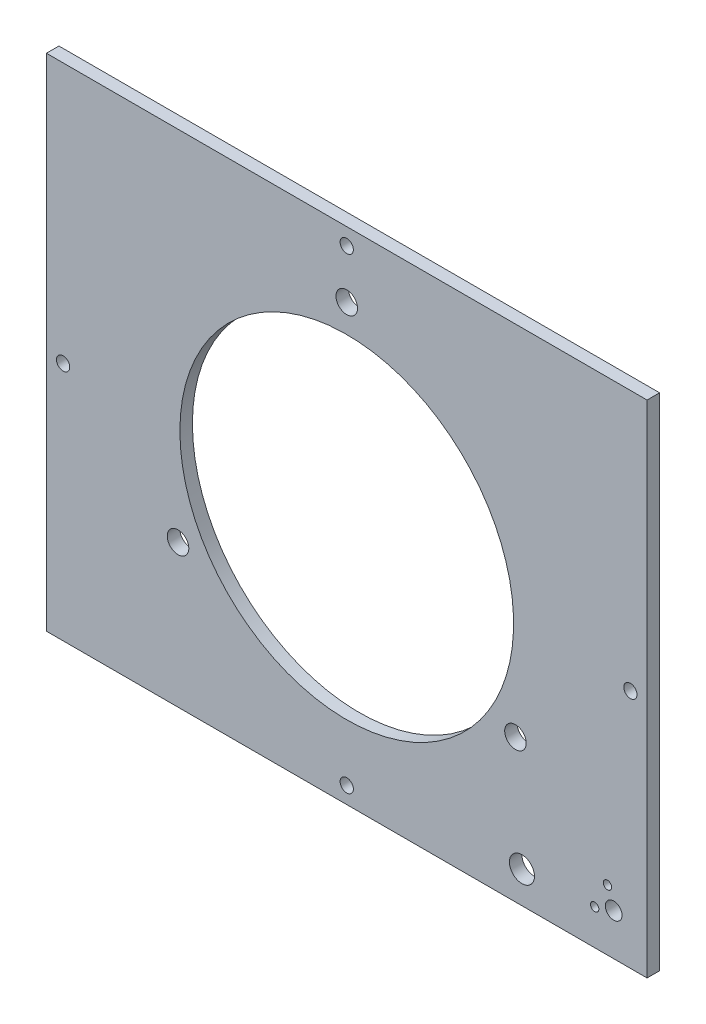
SolidWorks part; units mm, degrees
ref_plane "Front Plane" through (0, 0, 0) normal (0, 0, 1) x (1, 0, 0)
ref_plane "Top Plane" through (0, 0, 0) normal (0, 1, 0) x (1, 0, 0)
ref_plane "Right Plane" through (0, 0, 0) normal (1, 0, 0) x (0, 0, -1)
sketch "Sketch1" plane through (0, 0, 0) normal (0, 0, 1) x (1, 0, 0)
  line L0 (-228.6, -30.48) -> (-228.6, -182.88)
  line L1 (-228.6, -182.88) -> (228.6, -182.88)
  line L2 (-228.6, -182.88) -> (-228.6, 198.12) construction
  line L3 (-228.6, 198.12) -> (228.6, 198.12) construction
  line L4 (228.6, -182.88) -> (228.6, 198.12) construction
  line L5 (228.6, -30.48) -> (228.6, -182.88)
  line L6 (203.2, -151.13) -> (188.7233, -155.8925) construction
  line L7 (203.2, -151.13) -> (198.4375, -136.6533) construction
  line L10 (-228.6, -30.48) -> (-228.6, 198.12)
  line L11 (-228.6, 198.12) -> (228.6, 198.12)
  line L12 (228.6, -30.48) -> (228.6, 198.12)
  circle A0 centre (0, 0) radius 127
  circle A1 centre (0, 148.2852) radius 8.1988
  circle A3 centre (128.4188, -74.1426) radius 8.1988
  circle A4 centre (-128.4188, -74.1426) radius 8.1988
  circle A5 centre (203.2, -151.13) radius 6.35
  circle A6 centre (188.7233, -155.8925) radius 3.175
  circle A7 centre (198.4375, -136.6533) radius 3.175
  circle A8 centre (133.35, -158.75) radius 9.525
  point P19 (0, 0)
  dimension "D1" = 254
  dimension "D4" = 182.88
  dimension "D5" = 228.6
  dimension "D6" = 148.2852
  dimension "D8" = 12.7
  dimension "D9" = 31.75
  dimension "D10" = 25.4
  dimension "D11" = 15.24
  dimension "D12" = 6.35
  dimension "D13" = 26.9875
  dimension "D16" = 19.05
  dimension "D17" = 24.13
  dimension "D18" = 95.25
  dimension "D2" = 457.2
  dimension "D3" = 381
  dimension "D15" = 90
  dimension "D7" = 3
  dimension "D14" = 2
extrude "Boss-Extrude1" add sketch "Sketch1" along normal blind 9.525
sketch "Sketch2" plane through (0, 0, 9.525) normal (0, 0, 1) x (1, 0, 0)
  line L0 (-228.6, -182.88) -> (228.6, -182.88) construction
  line L1 (-228.6, 198.12) -> (-228.6, -182.88) construction
  line L2 (228.6, 198.12) -> (-228.6, 198.12) construction
  line L3 (228.6, -182.88) -> (228.6, 198.12) construction
  point P0 (0, 185.42)
  point P1 (-215.9, 0)
  point P2 (0, -170.18)
  point P3 (215.9, 0)
  point P4 (0, -182.88)
  dimension "D1" = 12.7
  dimension "D2" = 12.7
  dimension "D3" = 12.7
  dimension "D4" = 12.7
hole_wizard "3/8 Clearance Hole1" positions "Sketch4" profile "Sketch3" hole size "3/8" standard "ANSI Inch"
sketch "Sketch4" plane through (0, 0, 9.525) normal (0, 0, 1) x (1, 0, 0)
  point P0 (0, 185.42)
  point P3 (-215.9, 0)
  point P6 (0, -170.18)
  point P9 (215.9, 0)
sketch "Sketch3" plane through (0, 185.42, 9.525) normal (1, 0, 0) x (0, -1, 0)
  line L0 (0, 0) -> (0, 28.4295)
  line L1 (0, 28.4295) -> (5.0419, 25.4)
  line L2 (5.0419, 25.4) -> (5.0419, 0)
  line L5 (5.0419, 0) -> (0, 0)
  line L10 (0, 28.4295) -> (-5.0419, 25.4) construction
  line L11 (0, -6.35) -> (0, 107.95) construction
  dimension "Hole Dia." = 10.0838
  dimension "Hole Depth" = 25.4
  dimension "Drill Angle" = 118
